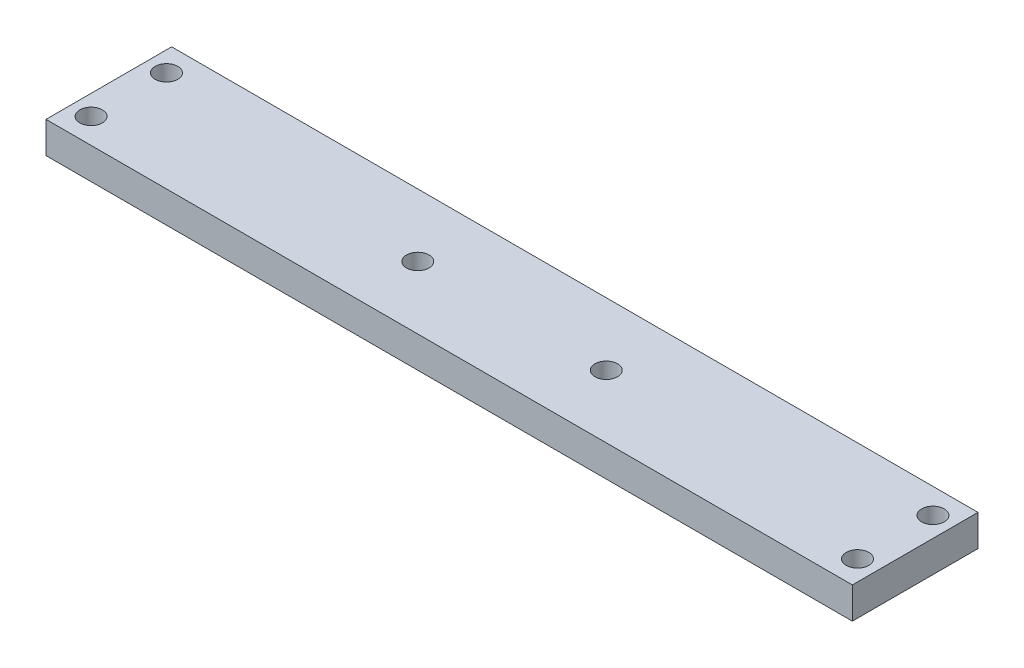
SolidWorks part; units mm, degrees
ref_plane "Front Plane" through (0, 0, 0) normal (0, 0, 1) x (1, 0, 0)
ref_plane "Top Plane" through (0, 0, 0) normal (0, 1, 0) x (1, 0, 0)
ref_plane "Right Plane" through (0, 0, 0) normal (1, 0, 0) x (0, 0, -1)
sketch "Sketch2" plane through (0, 0, 0) normal (0, 1, 0) x (1, 0, 0)
  line L1 (-39.8374, 20.9756) -> (88.5126, 20.9756)
  line L2 (-39.8374, 20.9756) -> (-39.8374, 0.9756)
  line L3 (-39.8374, 0.9756) -> (88.5126, 0.9756)
  line L4 (88.5126, 20.9756) -> (88.5126, 0.9756)
  dimension "D1" = 20
  dimension "D2" = 128.35
extrude "Boss-Extrude1" add sketch "Sketch2" along normal blind 5
sketch "Sketch3" plane through (0, 5, 0) normal (0, 1, 0) x (1, 0, 0)
  line L2 (-39.8374, 20.9756) -> (-39.8374, 0.9756) construction
  line L3 (88.5126, 0.9756) -> (88.5126, 20.9756) construction
  line L4 (-36.6624, 16.9756) -> (-36.6624, 4.9756) construction
  line L6 (-39.8374, 10.9756) -> (-36.6624, 10.9756) construction
  point P0 (-36.6624, 16.9756)
  point P1 (-36.6624, 4.9756)
  point P9 (85.3376, 16.9756)
  point P11 (85.3376, 4.9756)
  dimension "D1" = 12
  dimension "D3" = 3.175
  dimension "D4" = 3.175
  dimension "D5" = 3.175
  dimension "D6" = 122
hole_wizard "M3 Clearance Hole1" positions "Sketch3" profile "Sketch4" hole size "M3" standard "ANSI Metric" end condition through all
sketch "Sketch4" plane through (-36.6624, 5, -16.9756) normal (1, 0, 0) x (0, 0, 1)
  line L0 (0, 0) -> (0, 5)
  line L1 (0, 5) -> (1.8, 5)
  line L2 (1.8, 5) -> (1.8, 0)
  line L5 (1.8, 0) -> (0, 0)
  line L11 (0, -6.35) -> (0, 107.95) construction
  dimension "Thru Hole Dia." = 3.6
  dimension "Thru Hole Depth" = 5
sketch "Sketch5" plane through (0, 5, 0) normal (0, 1, 0) x (1, 0, 0)
  line L2 (9.3376, 10.9756) -> (39.3376, 10.9756) construction
  line L3 (88.5126, 20.9756) -> (-39.8374, 20.9756) construction
  line L4 (24.3376, 20.9756) -> (24.3376, 0.9756) construction
  line L5 (-39.8374, 0.9756) -> (88.5126, 0.9756) construction
  point P0 (9.3376, 10.9756)
  point P1 (39.3376, 10.9756)
  point P11 (24.3376, 10.9756)
  dimension "D1" = 30
hole_wizard "M3 Clearance Hole2" positions "Sketch5" profile "Sketch6" hole size "M3" standard "ANSI Metric" end condition through all
sketch "Sketch6" plane through (9.3376, 5, -10.9756) normal (1, 0, 0) x (0, 0, 1)
  line L0 (0, 0) -> (0, 5)
  line L1 (0, 5) -> (1.8, 5)
  line L2 (1.8, 5) -> (1.8, 0)
  line L5 (1.8, 0) -> (0, 0)
  line L11 (0, -6.35) -> (0, 107.95) construction
  dimension "Thru Hole Dia." = 3.6
  dimension "Thru Hole Depth" = 5
